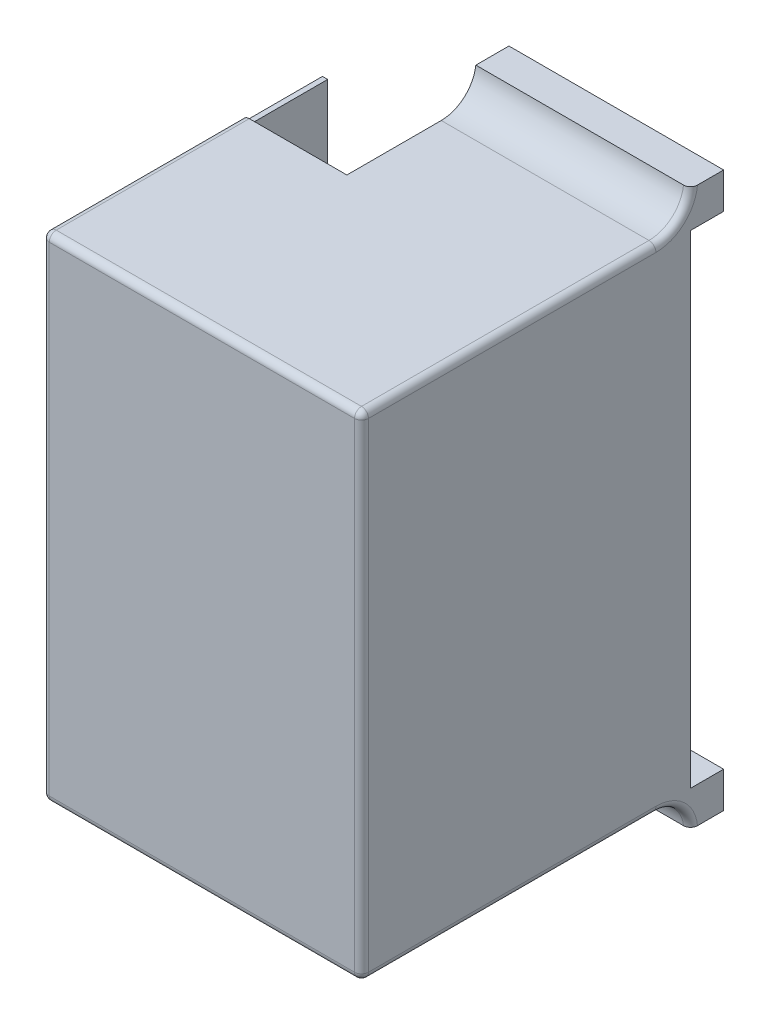
SolidWorks part; units mm, degrees
ref_plane "Front Plane" through (0, 0, 0) normal (1, 0, 0) x (0, 1, 0)
ref_plane "Top Plane" through (0, 0, 0) normal (0, 0, 1) x (0, 1, 0)
ref_plane "Right Plane" through (0, 0, 0) normal (0, 1, 0) x (-1, 0, 0)
sketch "Sketch1" plane through (0, 0, 0) normal (1, 0, 0) x (0, 1, 0)
  line L1 (0, 0) -> (141.6, 0)
  line L2 (0, 0) -> (0, 94.4)
  line L3 (0, 94.4) -> (141.6, 94.4)
  line L4 (141.6, 0) -> (141.6, 94.4)
  dimension "D1" = 94.4
  dimension "D2" = 141.6
extrude "Boss-Extrude1" add sketch "Sketch1" along normal blind 91.6
shell "Shell1" thickness 1.5 removed face at (45.8, 70.8, 0)
sketch "Sketch2" plane through (0, 0, 0) normal (-1, 0, 0) x (0, -1, 0)
  line L0 (0, 94.4) -> (0, 0) construction
  line L1 (-141.6, 0) -> (0, 0)
  line L2 (-141.6, 0) -> (-141.6, 14)
  line L3 (-141.6, 14) -> (0, 14)
  line L4 (0, 0) -> (0, 14)
  point P7 (-141.6, 7)
  dimension "D1" = 14
extrude "Cut-Extrude1" cut sketch "Sketch2" against normal blind 2
sketch "Sketch3" plane through (0, 141.6, 0) normal (0, 1, 0) x (1, 0, 0)
  line L0 (91.6, 0) -> (2, 0) construction
  line L1 (30, 0) -> (0, 0)
  line L2 (30, 0) -> (30, -37)
  line L3 (30, -37) -> (0, -37)
  line L4 (0, 0) -> (0, -37)
  line L5 (0, -14) -> (0, -94.4) construction
  dimension "D1" = 30
  dimension "D2" = 37
extrude "Cut-Extrude2" cut sketch "Sketch3" against normal blind 2
sketch "Sketch4" plane through (0, 0, 0) normal (0, 0, -1) x (1, 0, 0)
  line L0 (30, -140.1) -> (30, -141.6) construction
  line L1 (91.6, 0) -> (0, 0)
  line L2 (91.6, 0) -> (91.6, 8.8)
  line L3 (91.6, 8.8) -> (0, 8.8)
  line L4 (0, 0) -> (0, 8.8)
  line L5 (91.6, -141.6) -> (30, -141.6)
  line L6 (91.6, -141.6) -> (91.6, -150.4)
  line L7 (91.6, -150.4) -> (30, -150.4)
  line L8 (30, -141.6) -> (30, -150.4)
  dimension "D1" = 8.8
  dimension "D2" = 8.8
extrude "Boss-Extrude2" add sketch "Sketch4" along normal blind 9.5 separate body
sketch "Sketch5" plane through (0, 0, 0) normal (0, 0, -1) x (1, 0, 0)
  line L0 (0, 8.8) -> (0, 0) construction
  line L1 (91.6, 0) -> (0, 0)
  line L2 (91.6, 0) -> (91.6, -1.5)
  line L3 (91.6, -1.5) -> (0, -1.5)
  line L4 (0, 0) -> (0, -1.5)
  line L5 (90.1, -1.5) -> (2, -1.5) construction
  line L7 (91.6, -141.6) -> (30, -141.6)
  line L8 (91.6, -141.6) -> (91.6, -140.1)
  line L9 (91.6, -140.1) -> (30, -140.1)
  line L10 (30, -141.6) -> (30, -140.1)
extrude "Boss-Extrude3" add sketch "Sketch5" along normal up to surface (9.5 mm away) up to face at (60.8, 146, -9.5)
fillet "Fillet1" radius 10 2 edges at (46.8, 0, 0) (60.8, 141.6, 0)
sketch "Sketch6" plane through (0, 0, 0) normal (0, 0, 1) x (1, 0, 0)
  line L1 (0, -8.8) -> (2, -8.8)
  line L2 (0, -8.8) -> (0, 1.5)
  line L3 (0, 1.5) -> (2, 1.5)
  line L4 (2, -8.8) -> (2, 1.5)
extrude "Cut-Extrude3" cut sketch "Sketch6" against normal through all
fillet "Fillet2" radius 2 10 edges at (91.6, 144.1167, 3.2945) (91.6, -2.5167, 3.2945) (0, 0, 54.2) (0, 141.6, 65.7) (91.6, 141.6, 52.1639) (91.6, 0, 52.1639) (0, 70.8, 94.4) (45.8, 0, 94.4) (91.6, 70.8, 94.4) (45.8, 141.6, 94.4)
